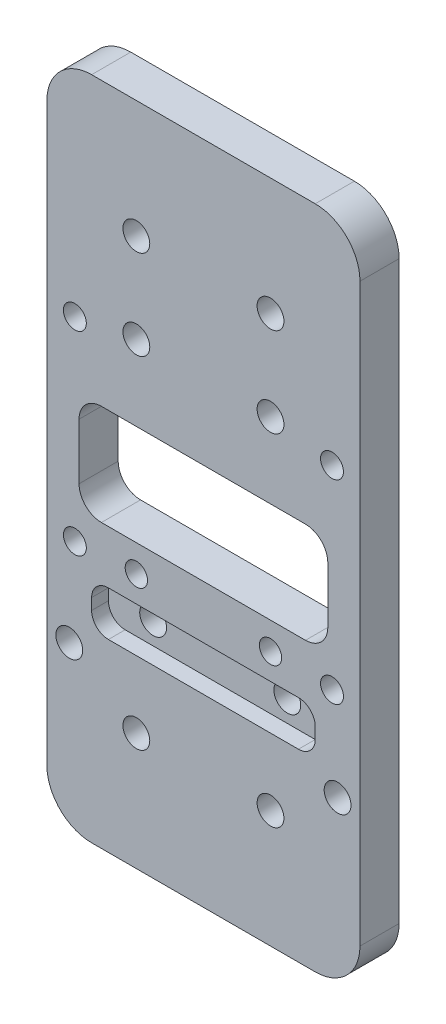
SolidWorks part; units mm, degrees
ref_plane "Plan de face" through (0, 0, 0) normal (0, 0, 1) x (1, 0, 0)
ref_plane "Plan de dessus" through (0, 0, 0) normal (0, 1, 0) x (1, 0, 0)
ref_plane "Plan de droite" through (0, 0, 0) normal (1, 0, 0) x (0, 0, -1)
sketch "Esquisse1" plane through (0, 0, 0) normal (0, 0, 1) x (1, 0, 0)
  line L1 (4, 0) -> (24, 0)
  line L2 (0, 4) -> (0, 55.5)
  line L3 (4, 59.5) -> (24, 59.5)
  line L4 (28, 4) -> (28, 55.5)
  arc A0 (28, 4) -> (24, 0) centre (24, 4) cw
  arc A1 (0, 4) -> (4, 0) centre (4, 4) ccw
  arc A2 (24, 59.5) -> (28, 55.5) centre (24, 55.5) cw
  arc A3 (0, 55.5) -> (4, 59.5) centre (4, 55.5) cw
  point P0 (28, 0.0312)
  point P9 (0, 0)
  point P12 (28, 59.5)
  point P15 (0, 59.5)
  point P17 (0, 0)
  dimension "D3" = 4
  dimension "D1" = 28
  dimension "D2" = 59.5
extrude "Boss.-Extru.1" add sketch "Esquisse1" along normal blind 3.5
sketch "Esquisse2" plane through (0, 0, 3.5) normal (0, 0, 1) x (1, 0, 0)
  line L0 (-3.9361, 18.5) -> (39.5369, 18.5) construction
  line L1 (14, -3.4341) -> (14, 66.5491) construction
  line L2 (0, 55.5) -> (0, 4) construction
  line L3 (4, 0) -> (24, 0) construction
  line L4 (8, -3.4341) -> (8, 61.0958) construction
  line L5 (20, 62.5518) -> (20, -2.6727) construction
  line L6 (-1.9394, 10.5) -> (40.0153, 10.5) construction
  line L7 (-3.9361, 49) -> (38.5954, 49) construction
  line L8 (-10.2317, 41) -> (41.5104, 41) construction
  line L9 (24, 59.5) -> (4, 59.5) construction
  line L10 (-2.7315, 40) -> (31.2638, 40) construction
  line L11 (-6.2586, 22.6) -> (34.9171, 22.6) construction
  line L12 (2.5, 73.0678) -> (2.5, -26.9316) construction
  line L13 (25.5, 66.5491) -> (25.5, -18.2006) construction
  circle A0 centre (8, 10.5) radius 1.2
  circle A1 centre (20, 10.5) radius 1.2
  circle A2 centre (8, 18.5) radius 1.2
  circle A3 centre (20, 18.5) radius 1.2
  circle A4 centre (8, 49) radius 1.2
  circle A5 centre (8, 41) radius 1.2
  circle A6 centre (20, 49) radius 1.2
  circle A7 centre (20, 41) radius 1.2
  circle A8 centre (2.5, 40) radius 1.025
  circle A9 centre (2.5, 22.6) radius 1.025
  circle A10 centre (25.5, 40) radius 1.025
  circle A11 centre (25.5, 22.6) radius 1.025
  dimension "D2" = 18.5
  dimension "D5" = 2.4
  dimension "D6" = 2.4
  dimension "D7" = 2.4
  dimension "D8" = 2.4
  dimension "D12" = 2.4
  dimension "D13" = 2.4
  dimension "D14" = 2.4
  dimension "D15" = 2.4
  dimension "D20" = 2.05
  dimension "D21" = 2.05
  dimension "D22" = 2.05
  dimension "D23" = 2.05
  dimension "D1" = 14
  dimension "D3" = 6
  dimension "D4" = 12
  dimension "D9" = 8
  dimension "D10" = 10.5
  dimension "D11" = 8
  dimension "D16" = 19.5
  dimension "D17" = 18.4
  dimension "D18" = 11.5
  dimension "D19" = 23
extrude "Enlèv. mat.-Extru.1" cut sketch "Esquisse2" against normal through all
sketch "Esquisse3" plane through (0, 0, 3.5) normal (0, 0, 1) x (1, 0, 0)
  line L0 (24, 59.5) -> (4, 59.5) construction
  line L1 (4.875, 34.25) -> (23.125, 34.25)
  line L2 (2.875, 32.25) -> (2.875, 27.25)
  line L3 (4.875, 25.25) -> (23.125, 25.25)
  line L4 (25.125, 32.25) -> (25.125, 27.25)
  line L5 (4, 0) -> (24, 0) construction
  line L6 (14, 63.5119) -> (14, -29.6665) construction
  line L7 (28, 4) -> (28, 55.5) construction
  arc A0 (25.125, 32.25) -> (23.125, 34.25) centre (23.125, 32.25) ccw
  arc A1 (25.125, 27.25) -> (23.125, 25.25) centre (23.125, 27.25) cw
  arc A2 (2.875, 27.25) -> (4.875, 25.25) centre (4.875, 27.25) ccw
  arc A3 (4.875, 34.25) -> (2.875, 32.25) centre (4.875, 32.25) ccw
  point P12 (14, 34.25)
  point P17 (25.125, 25.25)
  point P20 (2.875, 25.25)
  dimension "D5" = 2
  dimension "D1" = 25.25
  dimension "D2" = 25.25
  dimension "D3" = 22.25
  dimension "D4" = 14
extrude "Enlèv. mat.-Extru.2" cut sketch "Esquisse3" against normal through all
sketch "Esquisse7" plane through (0, 0, 3.5) normal (0, 0, 1) x (1, 0, 0)
  line L0 (4.875, 25.25) -> (23.125, 25.25) construction
  line L1 (0, 55.5) -> (0, 4) construction
  circle A0 centre (8, 22.82) radius 1
  circle A1 centre (20, 22.82) radius 1
  dimension "D1" = 2
  dimension "D2" = 2
  dimension "D3" = 12
  dimension "D4" = 2.43
  dimension "D5" = 8
extrude "Enlèv. mat.-Extru.4" cut sketch "Esquisse7" against normal through all
sketch "Esquisse9" plane through (0, 0, 3.5) normal (0, 0, 1) x (1, 0, 0)
  line L0 (0, 55.5) -> (0, 4) construction
  line L1 (4, 0) -> (24, 0) construction
  circle A0 centre (2, 14.5) radius 1.2
  circle A1 centre (26, 14.5) radius 1.2
  dimension "D1" = 24
  dimension "D4" = 2.4
  dimension "D5" = 2.4
  dimension "D2" = 2
  dimension "D3" = 14.5
extrude "Enlèv. mat.-Extru.6" cut sketch "Esquisse9" against normal through all
sketch "Esquisse10" plane through (0, 0, 3.5) normal (0, 0, 1) x (1, 0, 0)
  line L0 (-2.2067, 18.5) -> (33.6099, 18.5) construction
  line L1 (5.5, 20.5) -> (22.5, 20.5)
  line L2 (4, 19) -> (4, 18)
  line L3 (5.5, 16.5) -> (22.5, 16.5)
  line L4 (24, 19) -> (24, 18)
  line L5 (4.875, 25.25) -> (23.125, 25.25) construction
  line L6 (0, 55.5) -> (0, 4) construction
  arc A0 (4, 18) -> (5.5, 16.5) centre (5.5, 18) ccw
  arc A1 (5.5, 20.5) -> (4, 19) centre (5.5, 19) ccw
  arc A2 (22.5, 20.5) -> (24, 19) centre (22.5, 19) cw
  arc A3 (24, 18) -> (22.5, 16.5) centre (22.5, 18) cw
  point P8 (4, 18.5)
  point P13 (4, 16.5)
  point P16 (4, 20.5)
  point P19 (24, 20.5)
  dimension "D5" = 1.5
  dimension "D6" = 1.5
  dimension "D1" = 6.75
  dimension "D2" = 20
  dimension "D3" = 4
  dimension "D4" = 4
extrude "Enlèv. mat.-Extru.7" cut sketch "Esquisse10" against normal blind 1.5
